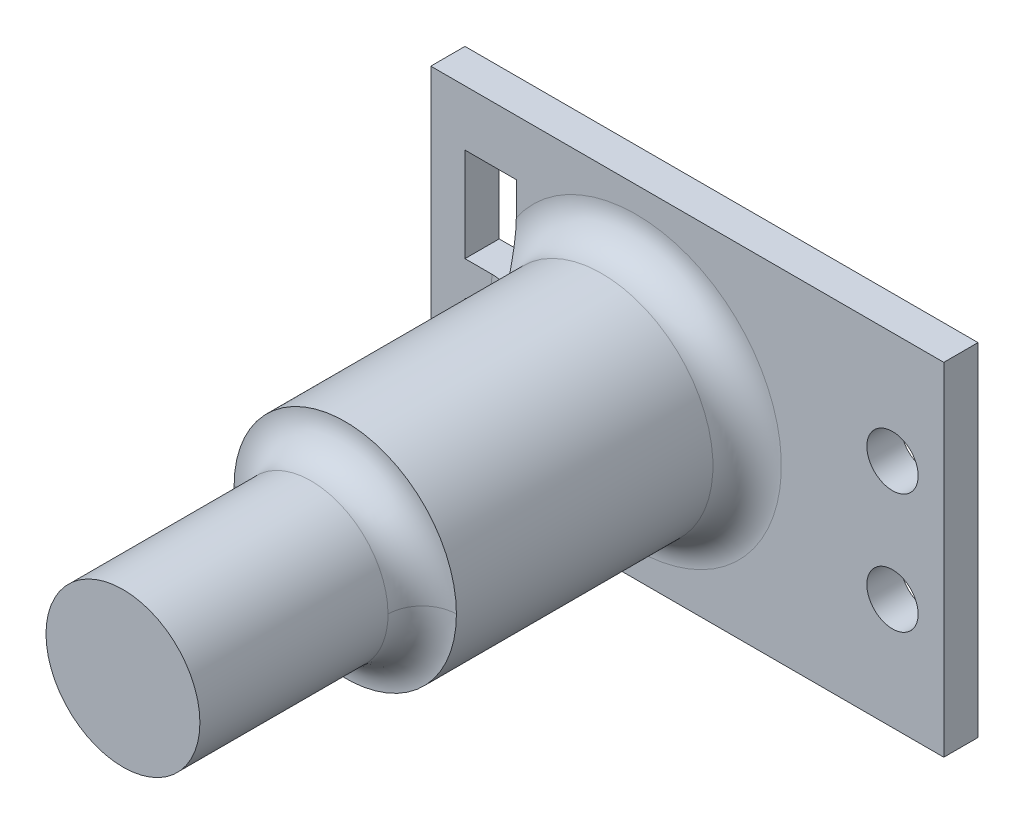
SolidWorks part; units mm, degrees
ref_plane "Plan de face" through (0, 0, 0) normal (0, 0, 1) x (1, 0, 0)
ref_plane "Plan de dessus" through (0, 0, 0) normal (0, 1, 0) x (1, 0, 0)
ref_plane "Plan de droite" through (0, 0, 0) normal (1, 0, 0) x (0, 0, -1)
sketch "Esquisse1" plane through (0, 0, 0) normal (0, 0, 1) x (1, 0, 0)
  line L1 (0, 0) -> (30, 0)
  line L2 (0, 0) -> (0, 20)
  line L3 (0, 20) -> (30, 20)
  line L4 (30, 0) -> (30, 20)
  dimension "D1" = 30
  dimension "D2" = 20
extrude "Boss.-Extru.1" add sketch "Esquisse1" along normal blind 2
sketch "Esquisse2" plane through (0, 0, 2) normal (0, 0, 1) x (1, 0, 0)
  line L1 (0, -0.0009) -> (0, 19.9991)
  line L2 (0, 19.9991) -> (30, 19.9991)
  line L3 (30, -0.0009) -> (30, 19.9991)
  circle A0 centre (12, 9.9991) radius 4.5
  dimension "D5" = 9
  dimension "D1" = 30
  dimension "D2" = 20
  dimension "D3" = 10
  dimension "D4" = 12
extrude "Boss.-Extru.2" add sketch "Esquisse2" along normal blind 30 contours A0 region at (12, 9.9991, 2)
sketch "Esquisse4" plane through (0, 0, 2) normal (0, 0, 1) x (1, 0, 0)
  line L1 (30, 0) -> (30, 20) construction
  line L2 (30, 20) -> (0, 20) construction
  circle A0 centre (12, 10) radius 6.5
  dimension "D3" = 13
  dimension "D1" = 18
  dimension "D2" = 10
extrude "Boss.-Extru.3" add sketch "Esquisse4" along normal blind 17
fillet "Congé1" radius 2 2 edges at (16.5, 9.9991, 19) (5.5, 10, 2)
sketch "Esquisse5" plane through (0, 0, 0) normal (0, 0, -1) x (-1, 0, 0)
  line L0 (-30, 0) -> (-30, 20) construction
  line L1 (-5, 16.75) -> (-2, 16.75)
  line L2 (-5, 16.75) -> (-5, 11.25)
  line L3 (-5, 11.25) -> (-2, 11.25)
  line L4 (-2, 16.75) -> (-2, 11.25)
  line L5 (-2, 9.25) -> (-5, 9.25)
  line L6 (-2, 9.25) -> (-2, 3.75)
  line L7 (-2, 3.75) -> (-5, 3.75)
  line L8 (-5, 9.25) -> (-5, 3.75)
  line L9 (0, 0) -> (-30, 0) construction
  line L10 (-30, 20) -> (0, 20) construction
  dimension "D1" = 25
  dimension "D2" = 25
  dimension "D3" = 3
  dimension "D4" = 2
  dimension "D5" = 5.5
  dimension "D6" = 5.5
  dimension "D7" = 3.75
  dimension "D8" = 3.25
  dimension "D9" = 3
extrude "Enlèv. mat.-Extru.1" cut sketch "Esquisse5" against normal blind 3
sketch "Esquisse6" plane through (0, 0, 2) normal (0, 0, 1) x (1, 0, 0)
  line L0 (30, 20) -> (0, 20) construction
  line L1 (0, 0) -> (30, 0) construction
  line L2 (30, 0) -> (30, 20) construction
  circle A0 centre (27, 13.5) radius 1.5
  circle A1 centre (27, 6.5) radius 1.5
  dimension "D5" = 3
  dimension "D6" = 3
  dimension "D1" = 6.5
  dimension "D2" = 6.5
  dimension "D3" = 3
  dimension "D4" = 3
extrude "Enlèv. mat.-Extru.2" cut sketch "Esquisse6" against normal through all
